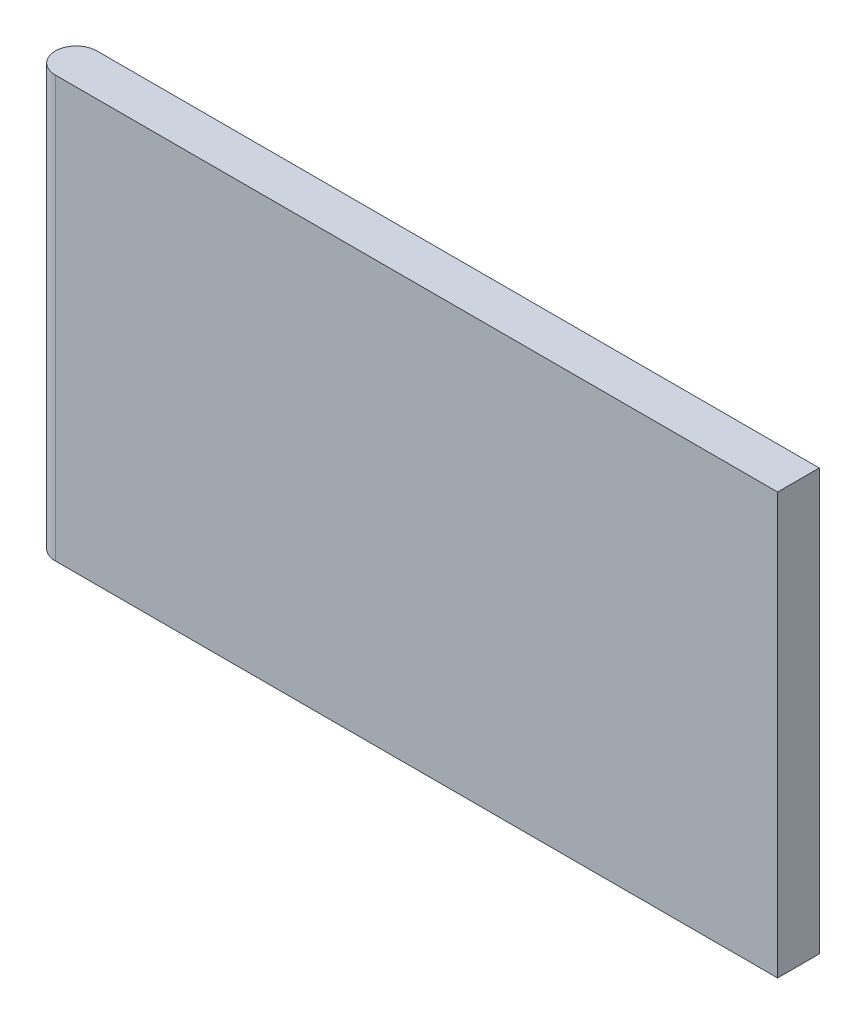
SolidWorks part; units mm, degrees
ref_plane "Front Plane" through (0, 0, 0) normal (0, 0, 1) x (1, 0, 0)
ref_plane "Top Plane" through (0, 0, 0) normal (0, 1, 0) x (1, 0, 0)
ref_plane "Right Plane" through (0, 0, 0) normal (1, 0, 0) x (0, 0, -1)
other "Center of Mass"
ref_plane "Plane2" through (0, 30.3, 0) normal (0, 1, 0) x (1, 0, 0)
sketch "Sketch1" plane through (0, 0, 0) normal (0, 1, 0) x (1, 0, 0)
  line L1 (-49.25, 1.5) -> (4.25, 1.5)
  line L2 (-49.25, 1.5) -> (-49.25, -1.5)
  line L3 (-49.25, -1.5) -> (4.25, -1.5)
  line L4 (4.25, 1.5) -> (4.25, -1.5)
  point P4 (4.25, 0)
  point P6 (0, 0)
  dimension "D1" = 53.5
  dimension "D2" = 4.25
  dimension "D3" = 3
extrude "Boss-Extrude1" add sketch "Sketch1" along normal up to surface (30.3 mm away) contours L4 L1 L3 | L2 L3 L1 region at (-22.5, 0, 0) up to plane "Plane2"
fillet "Fillet1" radius 1.5 2 edges at (-49.25, 15.15, -1.5) (-49.25, 15.15, 1.5)
ref_axis "Axis1" through (0, -7.6722, 0) along (0, 1, 0)
